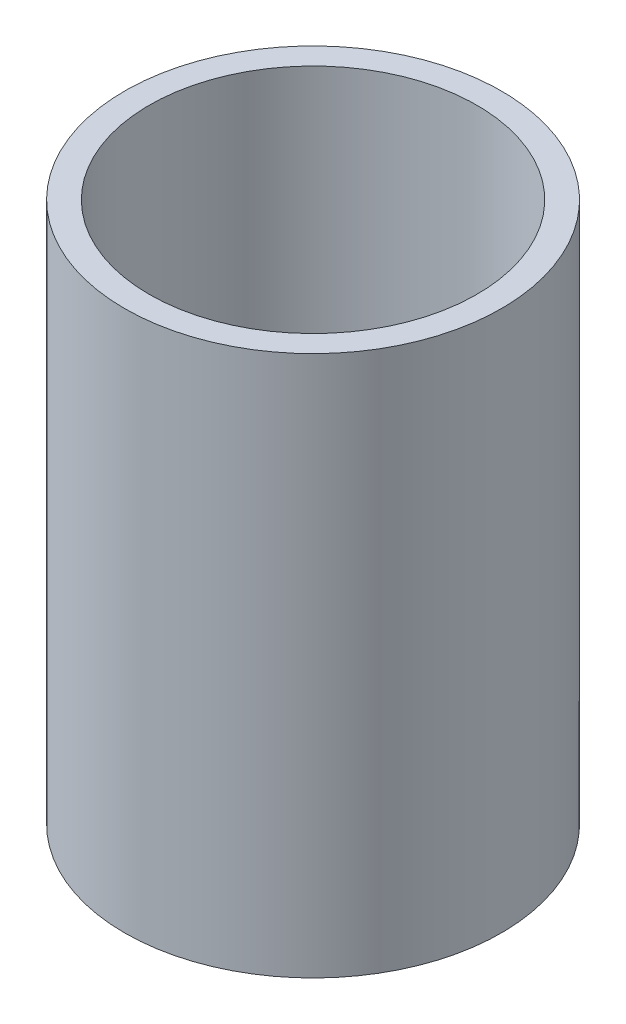
SolidWorks part; units mm, degrees
ref_plane "Front Plane" through (0, 0, 0) normal (0, 0, 1) x (1, 0, 0)
ref_plane "Top Plane" through (0, 0, 0) normal (0, 1, 0) x (1, 0, 0)
ref_plane "Right Plane" through (0, 0, 0) normal (1, 0, 0) x (0, 0, -1)
sketch "Sketch1" plane through (0, 0, 0) normal (0, 1, 0) x (1, 0, 0)
  circle A0 centre (0, 0) radius 23
  dimension "D1" = 46
extrude "Boss-Extrude1" add sketch "Sketch1" along normal blind 66
sketch "Sketch2" plane through (0, 0, 0) normal (0, -1, 0) x (1, 0, 0)
  circle A0 centre (0, 0) radius 20
  dimension "D1" = 40
extrude "Cut-Extrude1" cut sketch "Sketch2" against normal blind 17
sketch "Sketch4" plane through (0, 17, 0) normal (0, -1, 0) x (1, 0, 0)
  circle A0 centre (0, 0) radius 2
  dimension "D1" = 4
sketch "Sketch5" plane through (0, 66, 0) normal (0, 1, 0) x (1, 0, 0)
  circle A0 centre (0, 0) radius 20
  dimension "D1" = 40
extrude "Cut-Extrude2" cut sketch "Sketch5" against normal blind 40
extrude "Cut-Extrude3" cut sketch "Sketch4" against normal blind 40
